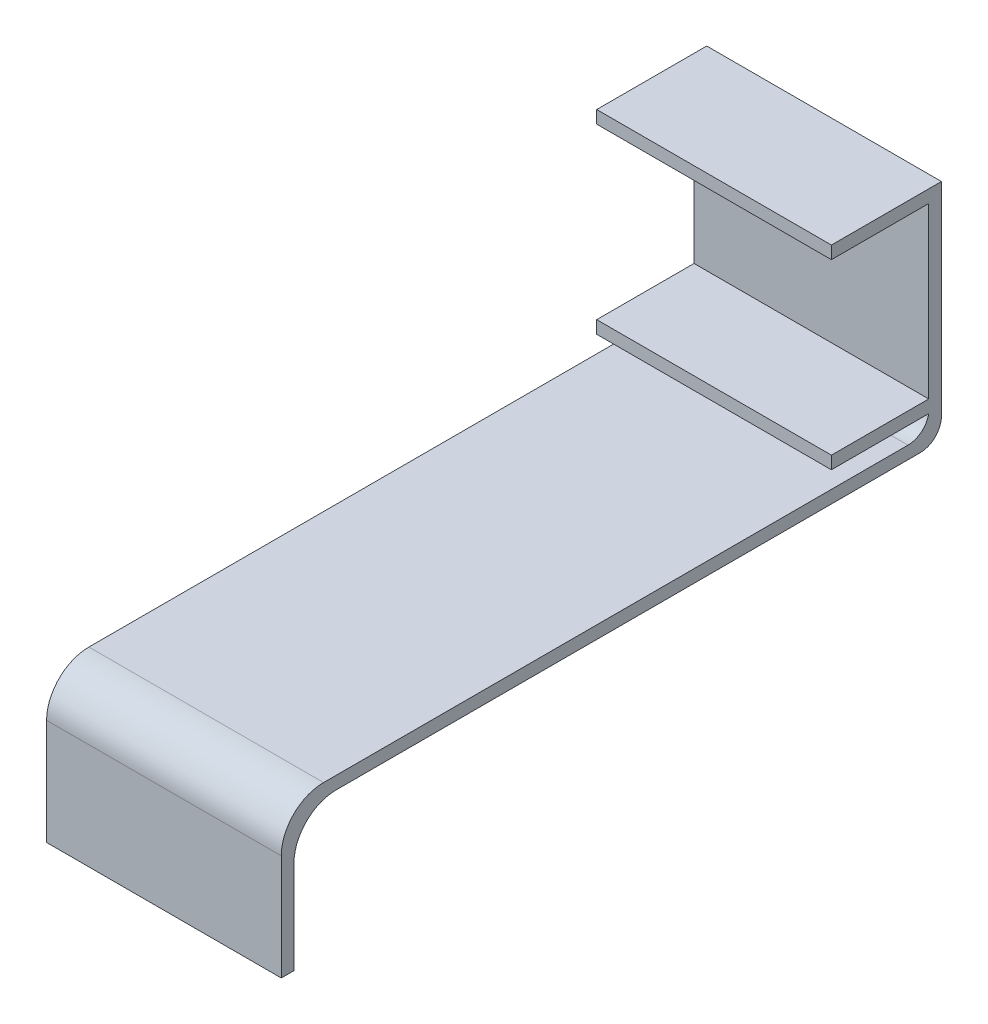
SolidWorks part; units mm, degrees
ref_plane "Front Plane" through (0, 0, 0) normal (0, 0, 1) x (1, 0, 0)
ref_plane "Top Plane" through (0, 0, 0) normal (0, 1, 0) x (1, 0, 0)
ref_plane "Right Plane" through (0, 0, 0) normal (1, 0, 0) x (0, 0, -1)
sketch "Sketch6" plane through (0, 0, 0) normal (0, 0, 1) x (1, 0, 0)
  line L1 (-27.7305, 26.5) -> (27.7305, 26.5)
  line L2 (-27.7305, 26.5) -> (-27.7305, -26.5)
  line L3 (-27.7305, -26.5) -> (27.7305, -26.5)
  line L4 (27.7305, 26.5) -> (27.7305, -26.5)
  line L5 (-27.7305, 26.5) -> (27.7305, -26.5) construction
  line L6 (-27.7305, -26.5) -> (27.7305, 26.5) construction
  point P0 (0, 0)
  dimension "D1" = 53
extrude "Boss-Extrude5" add sketch "Sketch6" along normal blind 3
sketch "Sketch7" plane through (0, 0, 3) normal (0, 0, 1) x (1, 0, 0)
  line L0 (27.7305, -26.5) -> (27.7305, 26.5) construction
  line L1 (-27.7305, 26.5) -> (27.7305, 26.5)
  line L2 (-27.7305, 26.5) -> (-27.7305, 23.5)
  line L3 (-27.7305, 23.5) -> (27.7305, 23.5)
  line L4 (27.7305, 26.5) -> (27.7305, 23.5)
  line L5 (-27.7305, 26.5) -> (-27.7305, -26.5) construction
  line L6 (-27.7305, -16.5) -> (27.7305, -16.5)
  line L7 (-27.7305, -16.5) -> (-27.7305, -19.5)
  line L8 (-27.7305, -19.5) -> (27.7305, -19.5)
  line L9 (27.7305, -16.5) -> (27.7305, -19.5)
  dimension "D1" = 3
  dimension "D2" = 3
  dimension "D3" = 40
extrude "Boss-Extrude6" add sketch "Sketch7" along normal blind 23
sketch "Sketch8" plane through (0, 0, 3) normal (0, 0, 1) x (1, 0, 0)
  line L0 (-27.7305, -19.5) -> (-27.7305, -26.5) construction
  line L1 (27.7305, -26.5) -> (-27.7305, -26.5)
  line L2 (27.7305, -26.5) -> (27.7305, -23.5)
  line L3 (27.7305, -23.5) -> (-27.7305, -23.5)
  line L4 (-27.7305, -26.5) -> (-27.7305, -23.5)
  dimension "D1" = 3
extrude "Boss-Extrude7" add sketch "Sketch8" along normal blind 150
sketch "Sketch9" plane through (0, 0, 153) normal (0, 0, 1) x (1, 0, 0)
  line L0 (-27.7305, -23.5) -> (-27.7305, -26.5) construction
  line L1 (27.7305, -23.5) -> (-27.7305, -23.5)
  line L2 (27.7305, -23.5) -> (27.7305, -58.5)
  line L3 (27.7305, -58.5) -> (-27.7305, -58.5)
  line L4 (-27.7305, -23.5) -> (-27.7305, -58.5)
  dimension "D1" = 35
extrude "Boss-Extrude8" add sketch "Sketch9" along normal blind 3
fillet "Fillet2" radius 10 1 edges at (0, -26.5, 153)
fillet "Fillet3" radius 10 1 edges at (0, -23.5, 156)
fillet "Fillet5" radius 5 1 edges at (0, -26.5, 0)
fillet "Fillet6" radius 5 1 edges at (0, -23.5, 3)
